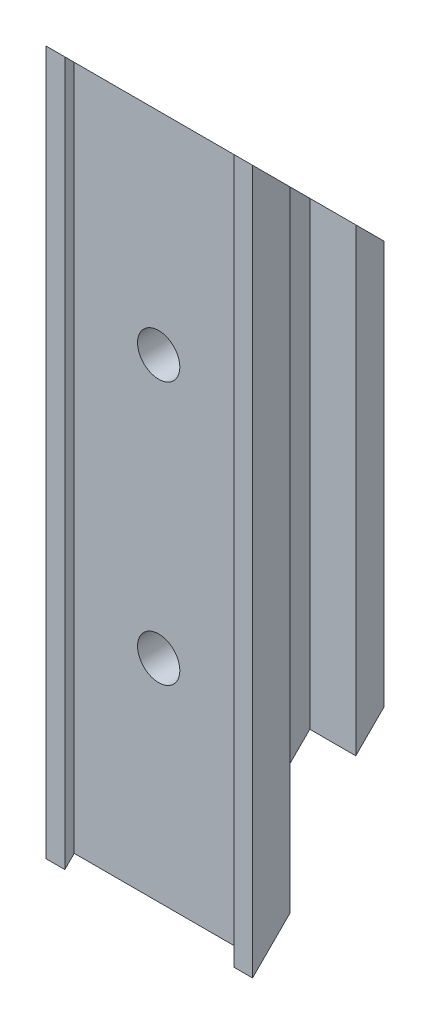
SolidWorks part; units mm, degrees
ref_plane "Front Plane" through (0, 0, 0) normal (0, 0, 1) x (1, 0, 0)
ref_plane "Top Plane" through (0, 0, 0) normal (0, 1, 0) x (1, 0, 0)
ref_plane "Right Plane" through (0, 0, 0) normal (1, 0, 0) x (0, 0, -1)
sketch "Sketch1" plane through (0, 0, 0) normal (0, 1, 0) x (1, 0, 0)
  line L0 (-9, 1) -> (9, 1)
  line L1 (9, 1) -> (9, 0)
  line L2 (9, 0) -> (11, 0)
  line L3 (11, 0) -> (11, 4)
  line L4 (11, 4) -> (4.1, 4)
  line L5 (4.1, 4) -> (4.1, 13)
  line L6 (4.1, 13) -> (9, 13)
  line L7 (9, 13) -> (9, 18)
  line L9 (9, 18) -> (-9, 18)
  line L10 (0, -55) -> (0, 55) construction
  line L12 (-9, 13) -> (-9, 18)
  line L13 (-4.1, 13) -> (-9, 13)
  line L14 (-4.1, 4) -> (-4.1, 13)
  line L15 (-11, 4) -> (-4.1, 4)
  line L16 (-11, 0) -> (-11, 4)
  line L17 (-9, 0) -> (-11, 0)
  line L18 (-9, 1) -> (-9, 0)
  point P0 (9, 38.8852)
  point P2 (0, 41.9471)
  point P24 (0, 1)
  dimension "D1" = 18
  dimension "D2" = 22
  dimension "D3" = 1
  dimension "D4" = 4
  dimension "D5" = 9
  dimension "D6" = 8.2
  dimension "D7" = 18
  dimension "D8" = 5
extrude "Boss-Extrude1" add sketch "Sketch1" along normal mid plane 75
chamfer "Chamfer1" distance 18 angle 45 2 edges at (0, -37.5, -18) (0, 37.5, -18)
chamfer "Chamfer2" distance 2 angle 45 2 edges at (-9, 0, -18) (9, 0, -18)
sketch "Sketch4" plane through (0, 0, -18) normal (0, 0, -1) x (-1, 0, 0)
  line L0 (9.9, 0) -> (-9.9, 0) construction
  line L1 (0, 9.9) -> (0, -9.9) construction
  point P0 (0, 14)
  point P5 (0, -14)
  point P6 (-2.1082, 14)
  point P7 (0, 14)
  dimension "D1" = 28
hole_wizard "CSK for M4 Countersunk Flat Head Screw1" positions "Sketch4" profile "Sketch3" countersink size "M4" standard "ISO" end condition through all
sketch "Sketch3" plane through (0, 14, -18) normal (1, 0, 0) x (0, 1, 0)
  line L0 (0, 0) -> (0, 18)
  line L1 (0, 18) -> (2.25, 18)
  line L2 (2.25, 18) -> (2.25, 2.45)
  line L3 (2.25, 2.45) -> (4.7, 0)
  line L5 (4.7, 0) -> (0, 0)
  line L6 (-2.25, 2.45) -> (-4.7, 0) construction
  line L11 (0, -6.35) -> (0, 107.95) construction
  dimension "Thru Hole Dia." = 4.5
  dimension "Thru Hole Depth" = 18
  dimension "Near C'Sink Dia." = 9.4
  dimension "Near C'Sink Angle" = 90
